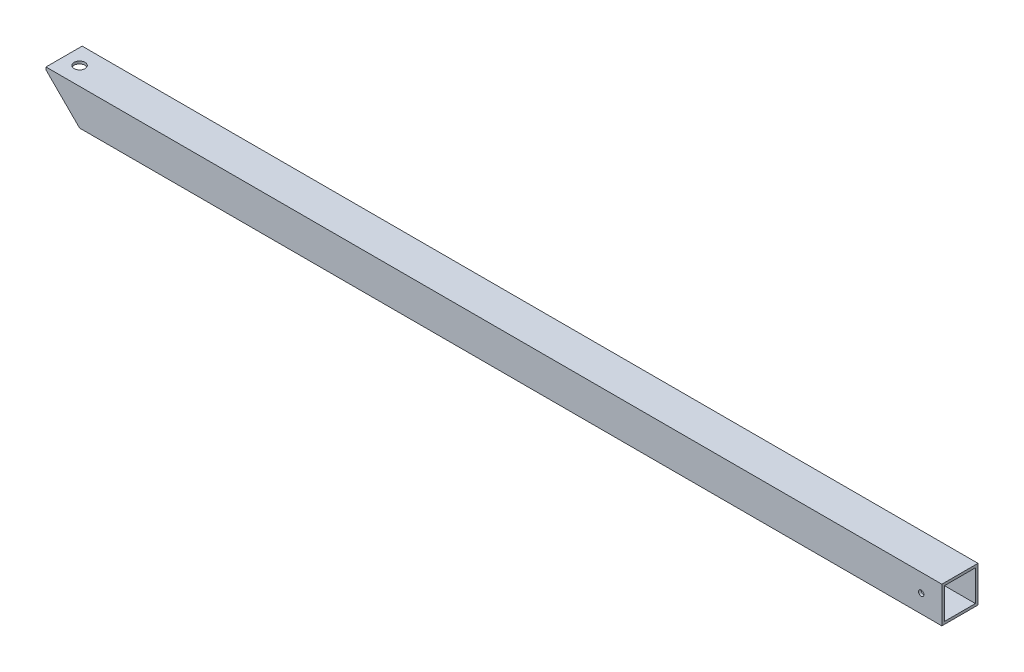
SolidWorks part; units mm, degrees
ref_plane "Front Plane" through (0, 0, 0) normal (0, 0, 1) x (1, 0, 0)
ref_plane "Top Plane" through (0, 0, 0) normal (0, 1, 0) x (1, 0, 0)
ref_plane "Right Plane" through (0, 0, 0) normal (1, 0, 0) x (0, 0, -1)
sketch "Sketch1" plane through (0, 0, 0) normal (0, 0, 1) x (1, 0, 0)
  line L1 (41.275, -44.45) -> (1101.725, -44.45)
  line L2 (1101.725, -44.45) -> (1101.725, 0)
  line L3 (1101.725, 0) -> (0, 0)
  line L4 (0, 0) -> (0, -3.175)
  line L5 (0, -3.175) -> (41.275, -44.45)
  circle A0 centre (1076.325, -22.225) radius 3.3147
  point P1 (50.0241, -84.3679)
  point P2 (0, 0)
  point P8 (1101.725, -22.225)
  dimension "D5" = 6.6294
  dimension "D1" = 44.45
  dimension "D2" = 3.175
  dimension "D3" = 1101.725
  dimension "D4" = 25.4
  dimension "D6" = 45
extrude "Boss-Extrude1" add sketch "Sketch1" along normal mid plane 44.45
shell "Shell1" thickness 3.175 removed face at (1079.6397, -22.225, 22.225) removed face at (1101.725, -22.225, 0) removed face at (0, -1.5875, 0) removed face at (20.6375, -23.8125, 0)
hole_wizard "1/2 Clearance Hole1" positions "Sketch2" profile "Sketch3" hole size "1/2" standard "ANSI Inch" end condition through all
sketch "Sketch2" plane through (0, 0, 0) normal (0, 1, 0) x (1, 0, 0)
  line L2 (0, -22.225) -> (0, 22.225) construction
  point P0 (19.05, 0)
  point P10 (0, 20.1308)
  point P15 (0, 0)
  dimension "D1" = 19.05
sketch "Sketch3" plane through (19.05, 0, 0) normal (1, 0, 0) x (0, 0, 1)
  line L0 (0, 0) -> (0, 44.45)
  line L1 (0, 44.45) -> (6.7462, 44.45)
  line L2 (6.7462, 44.45) -> (6.7462, 0)
  line L5 (6.7462, 0) -> (0, 0)
  line L11 (0, -6.35) -> (0, 107.95) construction
  dimension "Thru Hole Dia." = 13.4925
  dimension "Thru Hole Depth" = 44.45
